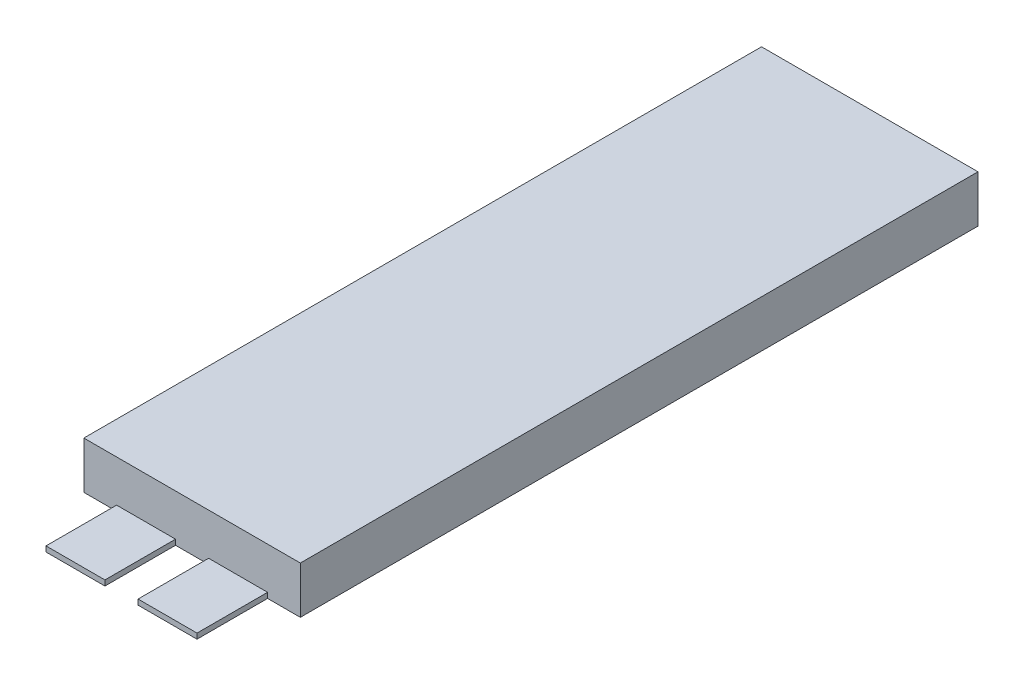
SolidWorks part; units mm, degrees
ref_plane "Front Plane" through (0, 0, 0) normal (0, 0, 1) x (1, 0, 0)
ref_plane "Top Plane" through (0, 0, 0) normal (0, 1, 0) x (1, 0, 0)
ref_plane "Right Plane" through (0, 0, 0) normal (1, 0, 0) x (0, 0, -1)
sketch "Sketch1" plane through (0, 0, 0) normal (0, 1, 0) x (1, 0, 0)
  line L2 (-23, 72) -> (23, 72)
  line L5 (-19, 72) -> (-19, 90)
  line L6 (-19, 90) -> (-4, 90)
  line L7 (-4, 90) -> (-4, 72)
  line L8 (4, 72) -> (4, 90)
  line L9 (4, 90) -> (19, 90)
  line L10 (19, 90) -> (19, 72)
  line L11 (0, 72) -> (0, 180.6197) construction
  line L13 (23, -72) -> (-23, -72)
  line L14 (23, -72) -> (23, 72)
  line L16 (-23, -72) -> (-23, 72)
  line L17 (23, -72) -> (-23, 72) construction
  line L18 (23, 72) -> (-23, -72) construction
  point P0 (0, 0)
  point P16 (-11.5, 90)
  point P17 (11.5, 90)
  dimension "D1" = 144
  dimension "D2" = 46
  dimension "D3" = 15
  dimension "D4" = 23
  dimension "D5" = 18
extrude "cell" add sketch "Sketch1" along normal blind 10 contours L2 L14 L13 L16
sketch "Sketch2" plane through (0, 0, 72) normal (0, 0, 1) x (1, 0, 0)
  line L0 (23, 0) -> (-23, 0) construction
  line L1 (-16.0434, 0) -> (-3.5183, 0)
  line L2 (-16.0434, 0) -> (-16.0434, 1.1329)
  line L3 (-16.0434, 1.1329) -> (-3.5183, 1.1329)
  line L4 (-3.5183, 0) -> (-3.5183, 1.1329)
  line L5 (0, 0) -> (0, 10) construction
  line L6 (23, 10) -> (-23, 10) construction
  line L7 (3.5183, 0) -> (3.5183, 1.1329)
  line L8 (16.0434, 1.1329) -> (3.5183, 1.1329)
  line L9 (16.0434, 0) -> (16.0434, 1.1329)
  line L10 (16.0434, 0) -> (3.5183, 0)
  point P9 (0, 0)
extrude "Boss-Extrude1" add sketch "Sketch2" along normal blind 15
equation "\"D1@cell\" = 10.00mm"
